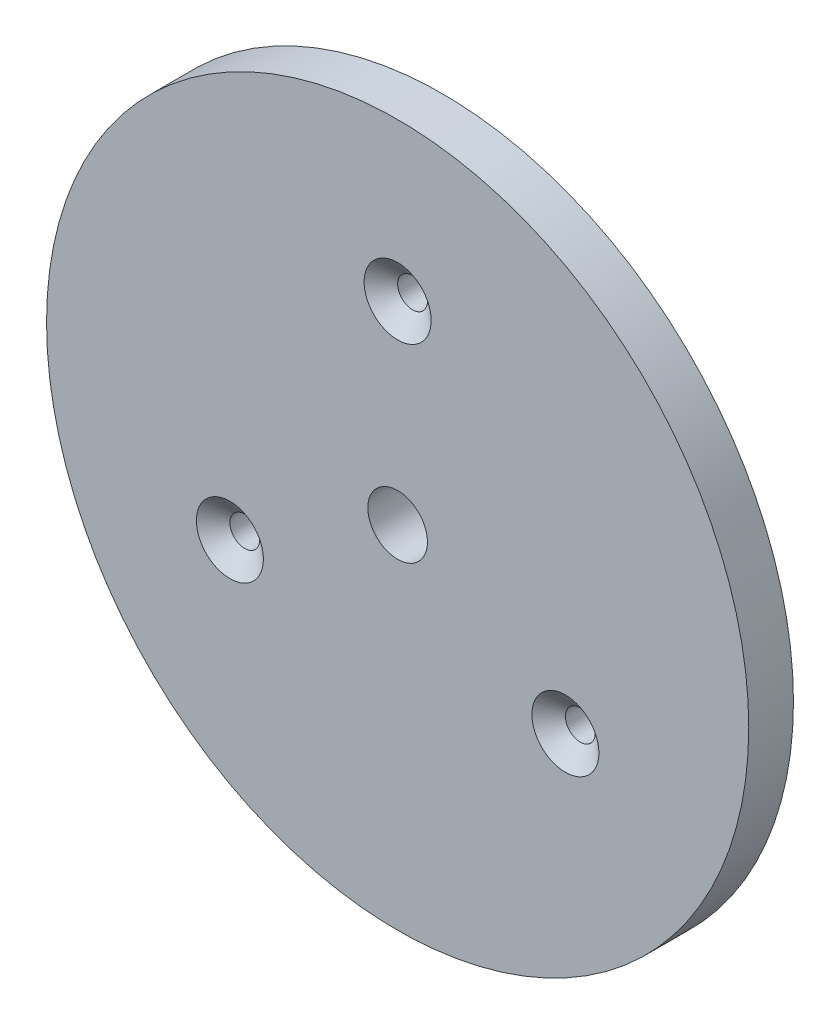
SolidWorks part; units mm, degrees
ref_plane "Front Plane" through (0, 0, 0) normal (1, 0, 0) x (0, 1, 0)
ref_plane "Top Plane" through (0, 0, 0) normal (0, 0, 1) x (0, 1, 0)
ref_plane "Right Plane" through (0, 0, 0) normal (0, 1, 0) x (-1, 0, 0)
sketch "Sketch3" plane through (0, 0, 0) normal (0, 0, 1) x (0, 1, 0)
  circle A0 centre (0, 0) radius 4
  circle A1 centre (0, 0) radius 26 construction
  circle A2 centre (0, 0) radius 47.125
  circle A3 centre (26, 0) radius 2
  circle A4 centre (-13, -22.5167) radius 2
  circle A5 centre (-13, 22.5167) radius 2
  dimension "D1" = 94.25
  dimension "D2" = 8
  dimension "D3" = 52
  dimension "D4" = 4
  dimension "D5" = 3
extrude "Boss-Extrude1" add sketch "Sketch3" along normal blind 6
chamfer "Chamfer1" distance 2.5 distance2 2 3 edges at (-20.5167, -13, 6) (24.5167, -13, 6) (2, 26, 6) first distance on face at (24.5167, -13, 6)
equation "\"SunTeeth\"= 12"
equation "\"PlanetTeeth\" = 40"
equation "\"Module\" = 1"
equation "\"OrbitDiameter\"= \"SunTeeth\" * \"Module\" + \"PlanetTeeth\" * \"Module\""
equation "\"SunBore\"= 8"
equation "\"D1@Sketch3\"= ( \"SunTeeth\" + 2 * \"PlanetTeeth\" ) * \"Module\" + 2.25 * \"Module\""
equation "\"D2@Sketch3\"=\"SunBore\""
equation "\"D3@Sketch3\"=\"OrbitDiameter\""
equation "\"BearingBore\" = 4"
equation "\"D4@Sketch3\"=\"BearingBore\""
equation "\"ScrewCircle\"=31"
equation "\"BearingDiameter\" = 13"
